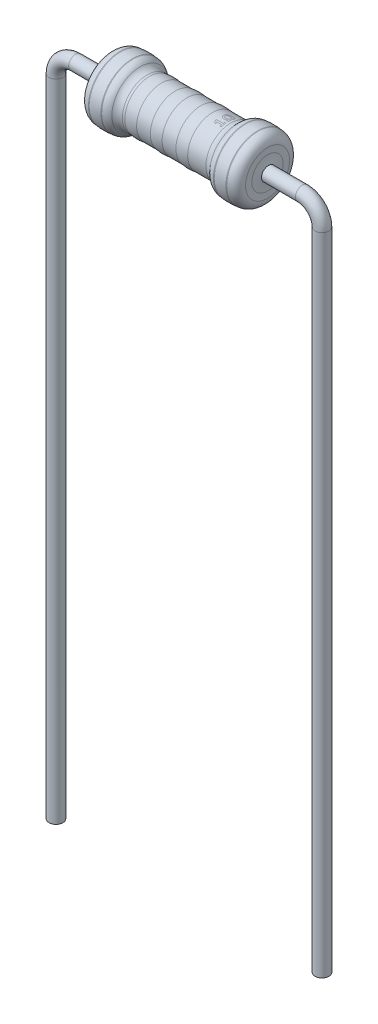
SolidWorks part; units mm, degrees
material "Plain Carbon Steel"
ref_plane "Front Plane" through (0, 0, 0) normal (0, 0, 1) x (1, 0, 0)
ref_plane "Top Plane" through (0, 0, 0) normal (0, 1, 0) x (1, 0, 0)
ref_plane "Right Plane" through (0, 0, 0) normal (1, 0, 0) x (0, 0, -1)
sketch "Sketch1" plane through (0, 0, 0) normal (0, 0, 1) x (1, 0, 0)
  line L0 (-4.33, 0) -> (4.33, 0)
  line L1 (-5.08, -0.75) -> (-5.08, -25.4)
  line L2 (5.08, -0.75) -> (5.08, -25.4)
  line L3 (-5.08, -25.4) -> (5.08, -25.4) construction
  line L4 (0, 0) -> (0, -25.4) construction
  arc A0 (-4.33, 0) -> (-5.08, -0.75) centre (-4.33, -0.75) ccw
  arc A1 (4.33, 0) -> (5.08, -0.75) centre (4.33, -0.75) cw
  dimension "D2" = 0.75
  dimension "D1" = 10.16
  dimension "D3" = 25.4
ref_plane "Plane1" through (-5.08, -25.4, 0) normal (0, -1, 0) x (-1, 0, 0)
sketch "Sketch2" plane through (-5.08, -25.4, 0) normal (0, -1, 0) x (-1, 0, 0)
  circle A0 centre (0, 0) radius 0.265
  dimension "D1" = 0.53
sweep "Sweep1" add profiles "Sketch2" path "Sketch1"
sketch "Sketch3" plane through (0, 0, 0) normal (0, 0, 1) x (1, 0, 0)
  line L0 (-3, 0) -> (3, 0)
  line L5 (-3, 0) -> (-3, 1.2)
  line L6 (3, 0) -> (3, 1.2)
  line L7 (-3, 1.2) -> (-1.8, 1.2)
  line L8 (3, 1.2) -> (1.8, 1.2)
  line L9 (-1.8, 1.2) -> (-1.8, 0.95)
  line L10 (-1.8, 0.95) -> (1.8, 0.95)
  line L11 (1.8, 0.95) -> (1.8, 1.2)
  line L12 (0, 0) -> (0, 0.95) construction
  dimension "D1" = 6
  dimension "D2" = 1.2
  dimension "D3" = 3.6
  dimension "D4" = 0.95
  dimension "D5" = 0.25
revolve "Revolve1" add sketch "Sketch3" angle 360 about L0
fillet "Fillet-1" radius 0.35 2 edges at (1.8, 0, 1.2) (-1.8, 0, 1.2)
fillet "Fillet-2" radius 0.36 4 edges at (3, 0, 1.2) (-3, 0, 1.2) (1.8, 0, 0.95) (-1.8, 0, 0.95)
sketch "Sketch5" plane through (0, 0, 0) normal (0, 0, 1) x (1, 0, 0)
  line L0 (-2.64, -1.2) -> (-2.1354, -1.2) construction
  line L5 (-2.3877, -1.2) -> (-2.3877, 0) construction
  line L10 (-3, 1.2) -> (-1.8, 1.2) construction
  line L15 (-1.05, 0.95) -> (-0.525, 0.95) construction
  line L16 (-3, 0) -> (3, 0) construction
  line L17 (-2.6127, 1.2) -> (-2.1627, 1.2) construction
  line L18 (-2.6127, 1.2) -> (-2.6127, 0) construction
  line L19 (-2.6127, 0) -> (-2.1627, 0) construction
  line L20 (-2.1627, 1.2) -> (-2.1627, 0) construction
  line L21 (-1.8, 0.95) -> (1.8, 0.95) construction
  line L22 (2.6127, 1.2) -> (2.1627, 1.2) construction
  line L23 (2.6127, 1.2) -> (2.6127, 0) construction
  line L24 (2.6127, 0) -> (2.1627, 0) construction
  line L25 (2.1627, 1.2) -> (2.1627, 0) construction
  line L26 (-1.05, 0.95) -> (-1.5, 0.95) construction
  line L27 (-1.05, 0.95) -> (-1.05, 0) construction
  line L28 (-1.05, 0) -> (-1.5, 0) construction
  line L29 (-1.5, 0.95) -> (-1.5, 0) construction
  line L30 (-2.3877, 1.2) -> (-2.3877, 1.22) construction
  line L31 (-0.075, 0.95) -> (-0.525, 0.95) construction
  line L32 (-0.075, 0.95) -> (-0.075, 0) construction
  line L33 (-0.075, 0) -> (-0.525, 0) construction
  line L34 (-0.525, 0.95) -> (-0.525, 0) construction
  line L35 (-1.275, 0.95) -> (-1.275, 0.97) construction
  line L36 (-0.3, 0.95) -> (-0.3, 0.97) construction
  line L37 (2.3877, 1.2) -> (2.3877, 1.22) construction
  line L39 (2.1354, -1.2) -> (2.64, -1.2) construction
  line L41 (2.3877, -1.2) -> (2.3877, 0) construction
  line L44 (3, 1.2) -> (1.8, 1.2) construction
  line L46 (-0.075, 0.95) -> (0.45, 0.95) construction
  line L48 (-3, 0) -> (-3, 0.6)
  line L49 (-3, 0) -> (-3, 1.2) construction
  line L50 (-3, 0) -> (-3.05, 0)
  line L51 (-3.05, 0) -> (-3.05, 0.2)
  line L52 (3, 0) -> (3.05, 0)
  line L53 (3.05, 0) -> (3.05, 0.2)
  line L54 (3, 0) -> (3, 0.6)
  line L55 (3, 0) -> (3, 1.2) construction
  line L56 (-1.05, 0) -> (-0.525, 0) construction
  line L58 (-0.075, 0) -> (0.45, 0) construction
  line L59 (0.45, 0) -> (0.45, 0.95) construction
  line L60 (0.45, 0) -> (0.9, 0) construction
  line L61 (0.9, 0) -> (0.9, 0.95) construction
  line L62 (1.5946, 0.95) -> (-1.5946, 0.95) construction
  line L63 (0.9, 0.95) -> (0.45, 0.95) construction
  line L64 (0.675, 0.95) -> (0.675, 0.97) construction
  arc A0 (-2.6127, 1.2) -> (-2.1627, 1.2) centre (-2.3877, -0.0556) cw construction
  arc A1 (-1.5, 0.95) -> (-1.05, 0.95) centre (-1.275, -0.3056) cw construction
  arc A2 (-0.525, 0.95) -> (-0.075, 0.95) centre (-0.3, -0.3056) cw construction
  arc A3 (2.1627, 1.2) -> (2.6127, 1.2) centre (2.3877, -0.0556) cw construction
  arc A6 (-3, 0.6) -> (-3.05, 0.2) centre (-4.625, 0.6) cw
  arc A7 (3.05, 0.2) -> (3, 0.6) centre (4.625, 0.6) cw
  arc A8 (0.45, 0.95) -> (0.9, 0.95) centre (0.675, -0.3056) cw construction
  dimension "D4" = 0.02
  dimension "D5" = 0.05
  dimension "D7" = 0.6
  dimension "D2" = 1.5
  dimension "D3" = 2.4
  dimension "D1" = 0.45
  dimension "D6" = 0.2
revolve "Revolve Ends" add sketch "Sketch5" angle 360 about L19
sketch "Sketch12" plane through (0, 0, 0) normal (0, 0, 1) x (1, 0, 0)
  line L0 (-2.6127, 0) -> (-2.1627, 0) construction
  line L1 (-2.6127, 0) -> (-2.1627, 0)
  line L2 (-2.6127, 1.2) -> (-2.6127, 0) construction
  line L3 (-2.6127, 1.2) -> (-2.6127, 0)
  line L4 (-2.1627, 1.2) -> (-2.1627, 0) construction
  line L5 (-2.1627, 1.2) -> (-2.1627, 0)
  arc A0 (-2.1627, 1.2) -> (-2.6127, 1.2) centre (-2.3877, -0.0556) ccw construction
  arc A1 (-2.1627, 1.2) -> (-2.6127, 1.2) centre (-2.3877, -0.0556) ccw
revolve "Revolve BAND 1" add sketch "Sketch12" angle 360 about L19
sketch "Sketch7" plane through (0, 0, 0) normal (0, 0, 1) x (1, 0, 0)
  line L0 (-1.05, 0) -> (-1.5, 0) construction
  line L1 (-1.05, 0.95) -> (-1.05, 0) construction
  line L2 (-1.5, 0.95) -> (-1.5, 0) construction
  line L3 (-1.05, 0.95) -> (-1.05, 0)
  line L4 (-1.5, 0.95) -> (-1.5, 0)
  line L5 (-1.05, 0) -> (-1.5, 0)
  arc A0 (-1.05, 0.95) -> (-1.5, 0.95) centre (-1.275, -0.3056) ccw construction
  arc A1 (-1.05, 0.95) -> (-1.5, 0.95) centre (-1.275, -0.3056) ccw
revolve "Revolve BAND 2" add sketch "Sketch7" angle 360 about L28
sketch "Sketch8" plane through (0, 0, 0) normal (0, 0, 1) x (1, 0, 0)
  line L0 (-0.075, 0.95) -> (-0.075, 0) construction
  line L1 (-0.075, 0) -> (-0.525, 0) construction
  line L2 (-0.525, 0.95) -> (-0.525, 0) construction
  line L3 (-0.075, 0.95) -> (-0.075, 0)
  line L4 (-0.075, 0) -> (-0.525, 0)
  line L5 (-0.525, 0.95) -> (-0.525, 0)
  arc A0 (-0.075, 0.95) -> (-0.525, 0.95) centre (-0.3, -0.3056) ccw construction
  arc A1 (-0.075, 0.95) -> (-0.525, 0.95) centre (-0.3, -0.3056) ccw
revolve "Revolve BAND 3" add sketch "Sketch8" angle 360 about L33
sketch "Sketch9" plane through (0, 0, 0) normal (0, 0, 1) x (1, 0, 0)
  line L0 (0.9, 0) -> (0.9, 0.95) construction
  line L1 (0.45, 0) -> (0.45, 0.95) construction
  line L2 (0.45, 0) -> (0.9, 0) construction
  line L3 (0.9, 0) -> (0.9, 0.95)
  line L4 (0.45, 0) -> (0.45, 0.95)
  line L5 (0.45, 0) -> (0.9, 0)
  arc A0 (0.9, 0.95) -> (0.45, 0.95) centre (0.675, -0.3056) ccw construction
  arc A1 (0.9, 0.95) -> (0.45, 0.95) centre (0.675, -0.3056) ccw
revolve "Revolve BAND 4" add sketch "Sketch9" angle 360 about L60
sketch "Sketch11" plane through (0, 0, 0) normal (0, 0, 1) x (1, 0, 0)
  line L0 (2.6127, 1.2) -> (2.6127, 0) construction
  line L1 (2.1627, 1.2) -> (2.1627, 0) construction
  line L2 (2.6127, 0) -> (2.1627, 0) construction
  line L3 (2.6127, 1.2) -> (2.6127, 0)
  line L4 (2.1627, 1.2) -> (2.1627, 0)
  line L5 (2.6127, 0) -> (2.1627, 0)
  arc A0 (2.6127, 1.2) -> (2.1627, 1.2) centre (2.3877, -0.0556) ccw construction
  arc A1 (2.6127, 1.2) -> (2.1627, 1.2) centre (2.3877, -0.0556) ccw
revolve "Revolve5" add sketch "Sketch11" angle 360 about L24
ref_plane "Plane2" through (0, 2, 0) normal (0, 1, 0) x (1, 0, 0)
sketch "Sketch6" plane through (0, 2, 0) normal (0, 1, 0) x (1, 0, 0)
  line L0 (0, 0) -> (1.5, 0) construction
  line L1 (1.5, 1) -> (1.5, -1) construction
  text T0 "1Ω" font "Calibri" height 0.3
  dimension "D1" = 1.5
  dimension "D2" = 2
wrap "Wrap1" sketch "Sketch6" wrap type scribe source sketch "Sketch6" face at (1.5946, 0, 0.95)
